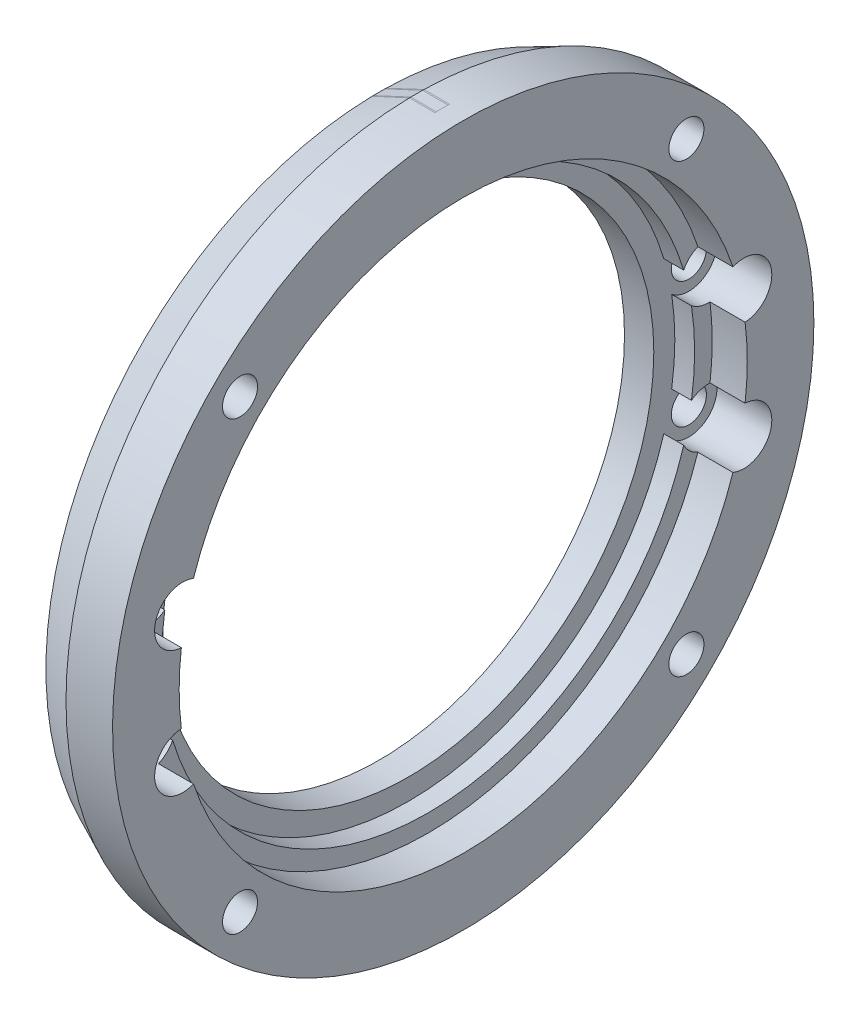
SolidWorks part; units mm, degrees
material "6061-T6 (SS)"
ref_plane "Front Plane" through (0, 0, 0) normal (0, 0, 1) x (1, 0, 0)
ref_plane "Top Plane" through (0, 0, 0) normal (0, 1, 0) x (1, 0, 0)
ref_plane "Right Plane" through (0, 0, 0) normal (1, 0, 0) x (0, 0, -1)
sketch "Sketch1" plane through (0, 0, 0) normal (1, 0, 0) x (0, 0, -1)
  line L0 (-0.9298, 49.9914) -> (0.9298, 49.9914)
  line L1 (-40, -9) -> (40, -9) construction
  line L2 (-40, -9) -> (-40, 9) construction
  line L3 (-40, 9) -> (40, 9) construction
  line L4 (40, -9) -> (40, 9) construction
  line L5 (-40, -9) -> (40, 9) construction
  line L6 (-40, 9) -> (40, -9) construction
  line L7 (-50, 0) -> (50, 0) construction
  line L8 (-0.9298, -49.9914) -> (0.9298, -49.9914)
  circle A0 centre (40, 9) radius 2.5 construction
  circle A1 centre (-40, 9) radius 2.5 construction
  circle A2 centre (-40, -9) radius 2.5 construction
  circle A3 centre (40, -9) radius 2.5 construction
  circle A4 centre (0, 0) radius 35
  arc A5 (-0.9298, 49.9914) -> (-0.9298, -49.9914) centre (0, 0) ccw
  arc A6 (0.9298, -49.9914) -> (0.9298, 49.9914) centre (0, 0) ccw
  point P0 (0, 0)
  point P18 (-0.9298, -49.9914)
  dimension "D3" = 5
  dimension "D4" = 5
  dimension "D5" = 5
  dimension "D6" = 5
  dimension "D7" = 70
  dimension "D8" = 100
  dimension "D1" = 80
  dimension "D2" = 18
extrude "Boss-Extrude1" add sketch "Sketch1" along normal blind 12
sketch "Sketch2" plane through (12, 0, 0) normal (1, 0, 0) x (0, 0, -1)
  circle A0 centre (0, 0) radius 38
  dimension "D1" = 76
extrude "Cut-Extrude1" cut sketch "Sketch2" against normal offset from surface (7.825 mm away) 4.175 up to face at (0, 0, 0)
sketch "Sketch3" plane through (12, 0, 0) normal (1, 0, 0) x (0, 0, -1)
  circle A0 centre (0, 0) radius 40.5
  dimension "D1" = 81
extrude "Cut-Extrude2" cut sketch "Sketch3" against normal blind 5
sketch "Sketch4" plane through (12, 0, 0) normal (1, 0, 0) x (0, 0, -1)
  circle A2 centre (0, 0) radius 50
  circle A5 centre (0, 0) radius 40.5 construction
  circle A6 centre (0, 0) radius 40.5
  dimension "D1" = 100
extrude "Boss-Extrude3" add sketch "Sketch4" against normal offset from surface (3 mm away) 2 up to face at (7, 0, -40.5)
fillet "Fillet1" radius 10 4 edges at (4.5, 49.9914, 0.9298) (4.5, 49.9914, -0.9298) (4.5, -49.9914, -0.9298) (4.5, -49.9914, 0.9298)
sketch "Sketch5" plane through (12, 0, 0) normal (1, 0, 0) x (0, 0, -1)
  circle A0 centre (40, 9) radius 2.5 construction
  circle A1 centre (40, -9) radius 2.5 construction
  circle A2 centre (-40, -9) radius 2.5 construction
  circle A3 centre (-40, 9) radius 2.5 construction
  circle A4 centre (40, 9) radius 2.5
  circle A5 centre (40, -9) radius 2.5
  circle A6 centre (-40, -9) radius 2.5
  circle A7 centre (-40, 9) radius 2.5
extrude "Cut-Extrude3" cut sketch "Sketch5" against normal through all
sketch "Sketch9" plane through (12, 0, 0) normal (1, 0, 0) x (0, 0, -1)
  line L0 (-40, 9) -> (-40, -9) construction
  line L1 (-40, -9) -> (40, -9) construction
  line L2 (40, -9) -> (40, 9) construction
  line L3 (40, 9) -> (-40, 9) construction
  line L4 (-40, 9) -> (-40, 0) construction
  line L5 (-40, 0) -> (40, 0) construction
  line L6 (40, 9) -> (40, 0) construction
  line L7 (0, 9) -> (0, -9) construction
  line L8 (40, 9) -> (40, -9) construction
  circle A0 centre (-40, 9) radius 4
  circle A1 centre (-40, -9) radius 4
  circle A2 centre (40, -9) radius 4
  circle A3 centre (40, 9) radius 4
  dimension "D1" = 8
extrude "Cut-Extrude4" cut sketch "Sketch9" against normal up to surface (7.825 mm away) up to face at (4.175, 0, -35)
chamfer "Chamfer2" distance 2.5 angle 65 8 edges at (0, 0, 50) (0, -49.9908, 0.9356) (0, 49.9908, 0.9356) (0, -49.9914, 0) (0, 49.9914, 0) (0, -49.9908, -0.9356) (0, 49.9908, -0.9356) (0, 0, -50) first distance on face at (0, 9, 37.5)
sketch "Sketch10" plane through (12, 0, 0) normal (1, 0, 0) x (0, 0, -1)
  line L0 (0, 0) -> (-45.726, 0) construction
  line L1 (0, 0) -> (-31.8198, 31.8198) construction
  line L2 (0, 0) -> (0, 50) construction
  circle A5 centre (0, 0) radius 50 construction
  circle A6 centre (-31.8198, 31.8198) radius 2.5
  circle A7 centre (31.8198, 31.8198) radius 2.5
  circle A8 centre (31.8198, -31.8198) radius 2.5
  circle A9 centre (-31.8198, -31.8198) radius 2.5
  point P17 (0, 0)
  dimension "D1" = 45
  dimension "D2" = 45
  dimension "D3" = 5
extrude "Cut-Extrude5" cut sketch "Sketch10" against normal offset from surface (7 mm away) 5 up to face at (0, 0, 0)
equation "\"d\"=5"
equation "\"D3@Sketch1\"=\"d\""
equation "\"D4@Sketch1\"=\"d\""
equation "\"D5@Sketch1\"=\"d\""
equation "\"D6@Sketch1\"=\"d\""
